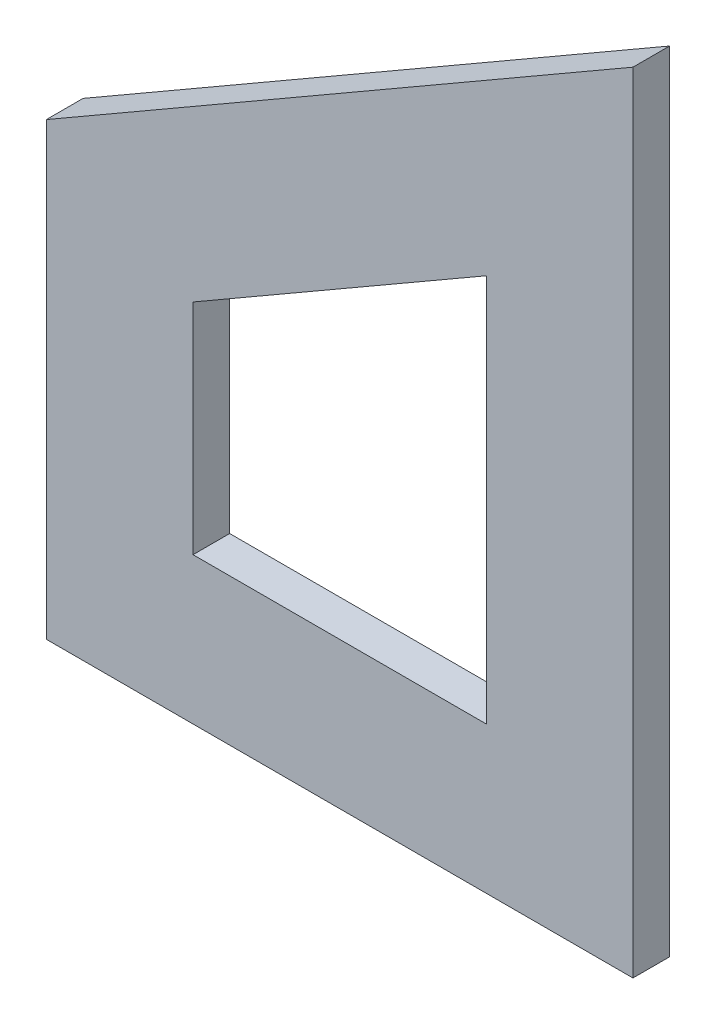
SolidWorks part; units mm, degrees
ref_plane "Front Plane" through (0, 0, 0) normal (0, 0, 1) x (1, 0, 0)
ref_plane "Top Plane" through (0, 0, 0) normal (0, 1, 0) x (1, 0, 0)
ref_plane "Right Plane" through (0, 0, 0) normal (1, 0, 0) x (0, 0, -1)
sketch "Sketch1" plane through (0, 0, 0) normal (0, 0, 1) x (1, 0, 0)
  line L0 (-130.8385, 95.25) -> (-29.2385, 95.25)
  line L1 (165.3114, 95.25) -> (-215.9, 95.25) construction
  line L2 (-29.2385, 95.25) -> (-29.2385, 231.8816)
  line L3 (-29.2385, 231.8816) -> (-130.8385, 173.2228)
  line L4 (-130.8385, 173.2228) -> (-130.8385, 95.25)
  line L5 (-130.8385, 173.2228) -> (-71.8403, 173.2228) construction
  line L6 (-130.8385, 173.2228) -> (-215.9, 124.1125) construction
  line L7 (0, -28.2875) -> (-285.4435, -28.2875) construction
  line L8 (-215.9, 95.25) -> (-215.9, 88.9) construction
  circle A0 centre (0, 20.925) radius 49.2125 construction
  dimension "D1" = 30
  dimension "D2" = 101.6
  dimension "D3" = 152.4
extrude "Boss-Extrude1" add sketch "Sketch1" along normal mid plane 6.35
sketch "Sketch2" plane through (0, 0, 3.175) normal (0, 0, 1) x (1, 0, 0)
  line L14 (-54.6385, 120.65) -> (-54.6385, 187.8875)
  line L15 (-105.4385, 120.65) -> (-54.6385, 120.65)
  line L16 (-105.4385, 158.5581) -> (-105.4385, 120.65)
  line L17 (-54.6385, 187.8875) -> (-105.4385, 158.5581)
  line L18 (-54.6385, 120.65) -> (-54.6385, 187.8875)
  line L19 (-105.4385, 120.65) -> (-54.6385, 120.65)
  line L20 (-105.4385, 158.5581) -> (-105.4385, 120.65)
  line L21 (-54.6385, 187.8875) -> (-105.4385, 158.5581)
  dimension "D1" = 25.4
extrude "Cut-Extrude1" cut sketch "Sketch2" against normal through all
